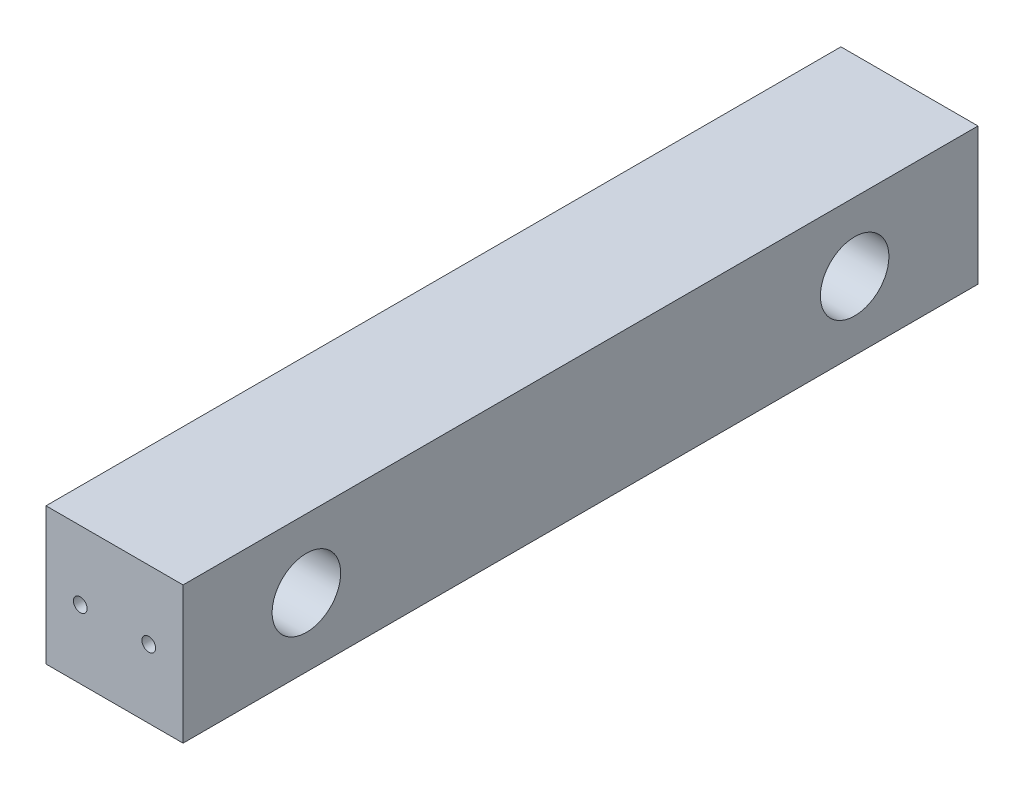
SolidWorks part; units mm, degrees
ref_plane "Front Plane" through (0, 0, 0) normal (0, 0, 1) x (1, 0, 0)
ref_plane "Top Plane" through (0, 0, 0) normal (0, 1, 0) x (1, 0, 0)
ref_plane "Right Plane" through (0, 0, 0) normal (1, 0, 0) x (0, 0, -1)
sketch "Sketch1" plane through (0, 0, 0) normal (0, 0, 1) x (1, 0, 0)
  line L0 (10, 0) -> (10, 20)
  line L1 (0, 0) -> (20, 0)
  line L2 (0, 0) -> (0, 20)
  line L3 (0, 20) -> (20, 20)
  line L4 (20, 0) -> (20, 20)
  circle A1 centre (15, 10) radius 1
  circle A2 centre (5, 10) radius 1
  point P9 (20, 10)
  dimension "D1" = 20
  dimension "D5" = 5
  dimension "D4" = 2
  dimension "D2" = 20
  dimension "D3" = 10
extrude "Boss-Extrude1" add sketch "Sketch1" along normal blind 116 contours L3 L4 L1 L2
ref_plane "Plane1" through (0, 0, 0) normal (0, 0, 1) x (1, 0, 0)
extrude "Cut-Extrude1" cut sketch "Sketch1<5>" along normal blind 10 contours A1 | A2
sketch "Sketch1<5>" plane through (0, 0, 0) normal (0, 0, 1) x (1, 0, 0) same geometry as "Sketch1"
ref_plane "Plane2" through (0, 0, 116) normal (0, 0, 1) x (1, 0, 0)
sketch "Sketch4" plane through (0, 0, 116) normal (0, 0, 1) x (1, 0, 0)
  line L0 (0, 20) -> (20, 20) construction
  line L1 (0, -11) -> (0, 11) construction
  line L2 (10, 20) -> (10, 0)
  line L3 (11, 0) -> (-11, 0) construction
  circle A0 centre (5, 10) radius 1
  circle A1 centre (15, 10) radius 1
  dimension "D1" = 2
  dimension "D2" = 10
  dimension "D3" = 5
extrude "Cut-Extrude2" cut sketch "Sketch4" against normal blind 10 contours A1 | A0
ref_plane "Plane4" through (20, 0, 0) normal (1, 0, 0) x (0, 0, -1)
sketch "Sketch5" plane through (20, 0, 0) normal (1, 0, 0) x (0, 0, -1)
  line L0 (-58, 20) -> (-58, 0)
  line L1 (-116, 20) -> (0, 20) construction
  line L2 (11, 0) -> (-11, 0) construction
  line L3 (-116, 11) -> (-116, -11) construction
  circle A0 centre (-98, 10) radius 2.5
  circle A1 centre (-18, 10) radius 2.5
  dimension "D1" = 5
  dimension "D2" = 18
  dimension "D3" = 10
extrude "Cut-Extrude3" cut sketch "Sketch5" against normal through all contours A0 | A1 region at (20, 10, 98) region at (20, 10, 18)
ref_plane "Plane5" through (20, 0, 0) normal (1, 0, 0) x (0, 0, -1)
sketch "Sketch6" plane through (20, 0, 0) normal (1, 0, 0) x (0, 0, -1)
  line L2 (-58, 20) -> (-58, 0)
  line L3 (-116, 20) -> (0, 20) construction
  line L4 (11, 0) -> (-11, 0) construction
  circle A0 centre (-98, 10) radius 5
  circle A1 centre (-18, 10) radius 5
  dimension "D1" = 10
extrude "Cut-Extrude4" cut sketch "Sketch6" against normal blind 10 contours A0 | A1 region at (20, 10, 98) region at (20, 10, 18)
